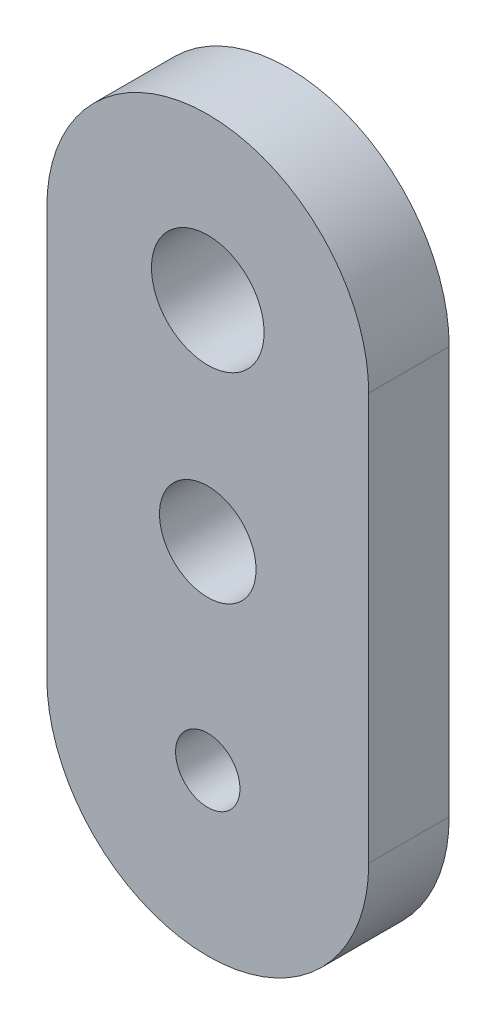
SolidWorks part; units mm, degrees
ref_plane "Front Plane" through (0, 0, 0) normal (0, 0, 1) x (1, 0, 0)
ref_plane "Top Plane" through (0, 0, 0) normal (0, 1, 0) x (1, 0, 0)
ref_plane "Right Plane" through (0, 0, 0) normal (1, 0, 0) x (0, 0, -1)
sketch "Sketch1" plane through (0, 0, 0) normal (0, 0, 1) x (1, 0, 0)
  line L0 (0, 0) -> (0, -25.3) construction
  line L1 (10, 0) -> (10, -25.3)
  line L2 (-10, 0) -> (-10, -25.3)
  circle A0 centre (0, 0) radius 3.5
  circle A1 centre (0, -13) radius 3
  circle A2 centre (0, -25.3) radius 2
  arc A3 (10, 0) -> (-10, 0) centre (0, 0) ccw
  arc A4 (-10, -25.3) -> (10, -25.3) centre (0, -25.3) ccw
  point P7 (0, -12.65)
  dimension "D1" = 4
  dimension "D2" = 6
  dimension "D3" = 7
  dimension "D5" = 7.3
  dimension "D4" = 13
  dimension "D6" = 20
extrude "Boss-Extrude1" add sketch "Sketch1" along normal blind 5
